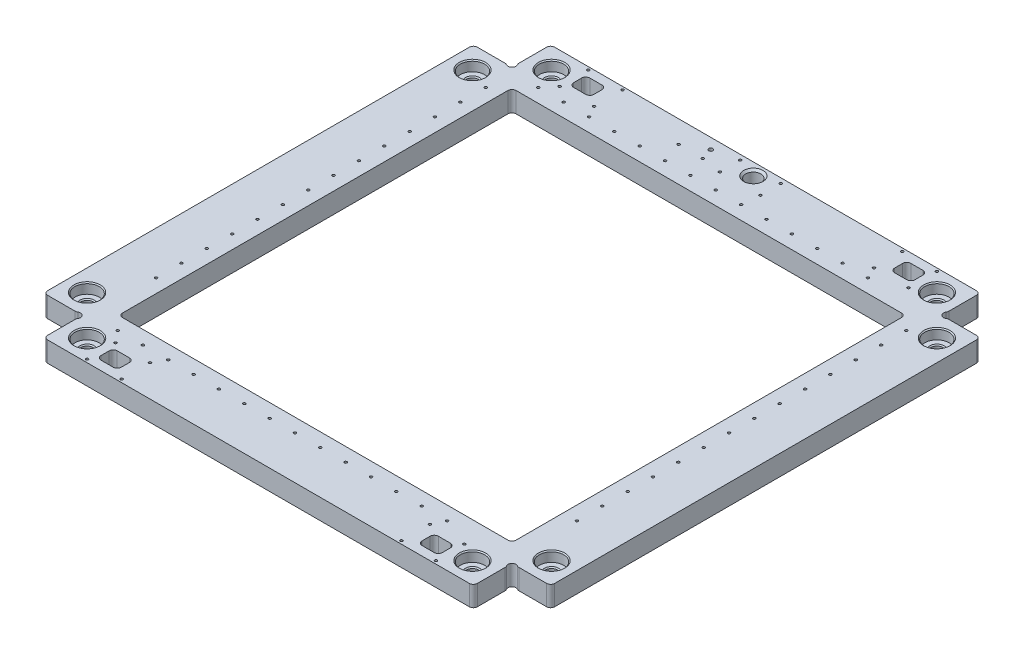
SolidWorks part; units mm, degrees
material "ASTM A36 Steel"
ref_plane "Front Plane" through (0, 0, 0) normal (0, 0, 1) x (1, 0, 0)
ref_plane "Top Plane" through (0, 0, 0) normal (0, 1, 0) x (1, 0, 0)
ref_plane "Right Plane" through (0, 0, 0) normal (1, 0, 0) x (0, 0, -1)
sketch "Sketch1" plane through (0, 0, 0) normal (0, 1, 0) x (1, 0, 0)
  line L1 (250, -250) -> (-250, -250)
  line L2 (250, -250) -> (250, 250)
  line L3 (250, 250) -> (-250, 250)
  line L4 (-250, -250) -> (-250, 250)
  line L5 (250, -250) -> (-250, 250) construction
  line L6 (250, 250) -> (-250, -250) construction
  point P0 (0, 0)
  dimension "D1" = 500
  dimension "D2" = 500
extrude "Boss-Extrude1" add sketch "Sketch1" along normal blind 20
sketch "Sketch2" plane through (0, 20, 0) normal (0, 1, 0) x (1, 0, 0)
  line L0 (250, 250) -> (-250, 250) construction
  line L10 (-250, 250) -> (-250, -250) construction
  line L15 (-250, 169) -> (-208, 169)
  line L16 (-250, 169) -> (-250, 211)
  line L17 (-174.5, 213.5) -> (-205.5, 213.5)
  line L27 (-250, 211) -> (-208, 211)
  line L33 (-208, 169) -> (-208, 211)
  line L35 (-250, 169) -> (-208, 211) construction
  line L36 (-250, 211) -> (-208, 169) construction
  line L37 (-169, 208) -> (-211, 208)
  line L38 (-169, 208) -> (-169, 250)
  line L39 (-169, 250) -> (-211, 250)
  line L40 (-211, 208) -> (-211, 250)
  line L41 (-169, 208) -> (-211, 250) construction
  line L42 (-169, 250) -> (-211, 208) construction
  line L43 (-208, 206) -> (-213, 211)
  line L44 (-174.5, 213.5) -> (-174.5, 244.5)
  line L45 (-174.5, 244.5) -> (-205.5, 244.5)
  line L46 (-205.5, 213.5) -> (-205.5, 244.5)
  line L47 (-174.5, 213.5) -> (-205.5, 244.5) construction
  line L48 (-174.5, 244.5) -> (-205.5, 213.5) construction
  line L49 (-213.5, 174.5) -> (-244.5, 174.5)
  line L50 (-213.5, 174.5) -> (-213.5, 205.5)
  line L51 (-213.5, 205.5) -> (-244.5, 205.5)
  line L52 (-244.5, 174.5) -> (-244.5, 205.5)
  line L53 (-213.5, 174.5) -> (-244.5, 205.5) construction
  line L54 (-213.5, 205.5) -> (-244.5, 174.5) construction
  line L55 (-206, 208) -> (-211, 213)
  line L56 (-213, 211) -> (-211, 213) construction
  point P1 (-229, 190)
  point P5 (-190, 229)
  point P23 (-229, 190)
  point P27 (-190, 229)
  dimension "D1" = 5
  dimension "D2" = 45
  dimension "D3" = 42
  dimension "D4" = 31
  dimension "D5" = 45
  dimension "D6" = 5
  dimension "D7" = 60
hole_wizard "Bearing Press Fit" positions "Sketch8" profile "Sketch9" hole size "Ø12.0" standard "ANSI Metric" end condition through all
sketch "Sketch8" plane through (0, 20, 0) normal (0, 1, 0) x (1, 0, 0)
  line L1 (-169, 250) -> (-211, 208) construction
  point P8 (-190, 229)
  point P12 (-229, 190)
sketch "Sketch9" plane through (-190, 20, -229) normal (1, 0, 0) x (0, 0, 1)
  line L0 (0, 0) -> (0, 20)
  line L1 (0, 20) -> (6, 20)
  line L2 (6, 20) -> (6, 0)
  line L5 (6, 0) -> (0, 0)
  line L11 (0, -6.35) -> (0, 107.95) construction
  dimension "Thru Hole Dia." = 12
  dimension "Thru Hole Depth" = 20
ref_axis "Axis1" through (0, 21, 0) along (0, -1, 0)
pattern_circular "CirPattern1" count 4 over 360 about axis through (0, 21, 0) along (0, -1, 0) of "Bearing Press Fit"
sketch "Sketch5" plane through (0, 20, 0) normal (0, 1, 0) x (1, 0, 0)
  line L1 (194, -194) -> (-194, -194)
  line L2 (194, -194) -> (194, 194)
  line L3 (194, 194) -> (-194, 194)
  line L4 (-194, -194) -> (-194, 194)
  line L5 (194, -194) -> (-194, 194) construction
  line L6 (194, 194) -> (-194, -194) construction
  point P0 (0, 0)
  dimension "D1" = 388
extrude "Cut-Extrude1" cut sketch "Sketch5" against normal up to surface (20 mm away) up to face at (-229, 0, 196)
sketch "Sketch10" plane through (0, 0, 0) normal (0, 1, 0) x (1, 0, 0)
  line L5 (194, 194) -> (-194, 194) construction
  line L6 (214, -214) -> (-214, -214)
  line L14 (214, -214) -> (214, 214)
  line L15 (214, 214) -> (-214, 214)
  line L16 (-214, -214) -> (-214, 214)
  line L17 (214, -214) -> (-214, 214) construction
  line L18 (214, 214) -> (-214, -214) construction
  line L19 (201.5, -201.5) -> (-201.5, -201.5)
  line L20 (201.5, -201.5) -> (201.5, 201.5)
  line L21 (201.5, 201.5) -> (-201.5, 201.5)
  line L22 (-201.5, -201.5) -> (-201.5, 201.5)
  line L23 (201.5, -201.5) -> (-201.5, 201.5) construction
  line L24 (201.5, 201.5) -> (-201.5, -201.5) construction
  point P0 (0, 0)
  point P6 (0, 0)
  dimension "D2" = 7.5
  dimension "D1" = 12.5
extrude "Linear Rail Slot" cut sketch "Sketch10" along normal blind 2.5
fillet "Fillet2" radius 4 4 edges at (-194, 10, 194) (194, 10, 194) (194, 10, -194) (-194, 10, -194)
sketch "Sketch11" plane through (0, 2.5, 0) normal (0, -1, 0) x (1, 0, 0)
  line L0 (-204, 207.5) -> (156, 207.5)
  line L1 (-201.5, 201.5) -> (201.5, 201.5) construction
  line L3 (-214, -214) -> (-214, 214) construction
  point P16 (143.5, 207.5)
  point P18 (118.5, 207.5)
  point P19 (93.5, 207.5)
  point P20 (68.5, 207.5)
  point P21 (43.5, 207.5)
  point P22 (18.5, 207.5)
  point P23 (-6.5, 207.5)
  point P24 (-31.5, 207.5)
  point P25 (-56.5, 207.5)
  point P26 (-81.5, 207.5)
  point P28 (-106.5, 207.5)
  point P29 (-131.5, 207.5)
  point P30 (-156.5, 207.5)
  point P31 (-181.5, 207.5)
  dimension "D1" = 360
  dimension "D2" = 6
  dimension "D4" = 14
  dimension "D5" = 25
  dimension "D6" = 10
  dimension "D3" = 12.5
hole_wizard "Tap Drill for M3x0.5 Tap1" positions "Sketch12" profile "Sketch13" hole size "M3x0.5" standard "ANSI Metric" end condition through all
sketch "Sketch12" plane through (0, 2.5, 0) normal (0, -1, 0) x (-1, 0, 0)
  line L0 (204, -207.5) -> (-156, -207.5) construction
  point P28 (-143.5, -207.5)
  point P31 (-118.5, -207.5)
  point P34 (-93.5, -207.5)
  point P37 (-68.5, -207.5)
  point P40 (-43.5, -207.5)
  point P43 (-18.5, -207.5)
  point P46 (6.5, -207.5)
  point P49 (31.5, -207.5)
  point P51 (56.5, -207.5)
  point P54 (81.5, -207.5)
  point P57 (106.5, -207.5)
  point P61 (131.5, -207.5)
  point P64 (156.5, -207.5)
  point P67 (181.5, -207.5)
sketch "Sketch13" plane through (143.5, 2.5, 207.5) normal (1, 0, 0) x (0, 0, -1)
  line L0 (0, 0) -> (0, 17.5)
  line L1 (0, 17.5) -> (1.25, 17.5)
  line L2 (1.25, 17.5) -> (1.25, 0)
  line L5 (1.25, 0) -> (0, 0)
  line L11 (0, -6.35) -> (0, 107.95) construction
  dimension "Thru Hole Dia." = 2.5
  dimension "Thru Hole Depth" = 17.5
sketch "Sketch14" plane through (0, 0, 0) normal (0, -1, 0) x (1, 0, 0)
  line L1 (-156.5, 213.5) -> (-181.5, 213.5)
  line L2 (-152.5, 217.5) -> (-152.5, 219.5)
  line L3 (-156.5, 223.5) -> (-181.5, 223.5)
  line L4 (-185.5, 217.5) -> (-185.5, 219.5)
  line L5 (-152.5, 213.5) -> (-185.5, 223.5) construction
  line L6 (-152.5, 223.5) -> (-185.5, 213.5) construction
  line L7 (-201.5, 201.5) -> (201.5, 201.5) construction
  line L8 (-181.5, 207.5) -> (-156.5, 207.5) construction
  line L19 (-6.5, 213.5) -> (-31.5, 213.5)
  line L25 (-2.5, 217.5) -> (-2.5, 219.5)
  line L26 (-6.5, 223.5) -> (-31.5, 223.5)
  line L31 (-35.5, 217.5) -> (-35.5, 219.5)
  line L32 (-2.5, 213.5) -> (-35.5, 223.5) construction
  line L33 (-2.5, 223.5) -> (-35.5, 213.5) construction
  line L34 (-31.5, 207.5) -> (-6.5, 207.5) construction
  line L35 (143.5, 213.5) -> (118.5, 213.5)
  line L36 (147.5, 217.5) -> (147.5, 219.5)
  line L37 (143.5, 223.5) -> (118.5, 223.5)
  line L38 (114.5, 217.5) -> (114.5, 219.5)
  line L39 (147.5, 213.5) -> (114.5, 223.5) construction
  line L40 (147.5, 223.5) -> (114.5, 213.5) construction
  line L41 (118.5, 207.5) -> (143.5, 207.5) construction
  arc A3 (-152.5, 219.5) -> (-156.5, 223.5) centre (-156.5, 219.5) ccw
  arc A4 (-156.5, 213.5) -> (-152.5, 217.5) centre (-156.5, 217.5) ccw
  arc A5 (-181.5, 213.5) -> (-185.5, 217.5) centre (-181.5, 217.5) cw
  arc A6 (-181.5, 223.5) -> (-185.5, 219.5) centre (-181.5, 219.5) ccw
  arc A7 (-2.5, 219.5) -> (-6.5, 223.5) centre (-6.5, 219.5) ccw
  arc A8 (-6.5, 213.5) -> (-2.5, 217.5) centre (-6.5, 217.5) ccw
  arc A9 (-31.5, 213.5) -> (-35.5, 217.5) centre (-31.5, 217.5) cw
  arc A10 (-31.5, 223.5) -> (-35.5, 219.5) centre (-31.5, 219.5) ccw
  arc A11 (147.5, 219.5) -> (143.5, 223.5) centre (143.5, 219.5) ccw
  arc A12 (143.5, 213.5) -> (147.5, 217.5) centre (143.5, 217.5) ccw
  arc A13 (118.5, 213.5) -> (114.5, 217.5) centre (118.5, 217.5) cw
  arc A14 (118.5, 223.5) -> (114.5, 219.5) centre (118.5, 219.5) ccw
  point P0 (-169, 218.5)
  point P12 (-169, 207.5)
  point P26 (-19, 218.5)
  point P45 (131, 218.5)
  dimension "D5" = 3
  dimension "D4" = 4
  dimension "D1" = 33
  dimension "D2" = 12
  dimension "D3" = 10
  dimension "D7" = 25
  dimension "D6" = 150
mirror "Mirror5" about plane through (0, 0, 0) normal (0, 0, 1) of "Tap Drill for M3x0.5 Tap1"
ref_plane "Plane1" through (0, 0, 0) normal (-0.7071, 0, 0.7071) x (0.7071, 0, 0.7071)
mirror "Mirror6" about plane through (0, 0, 0) normal (-0.7071, 0, 0.7071) of "Mirror5"
sketch "Sketch19" plane through (0, 2.5, 0) normal (0, -1, 0) x (1, 0, 0)
  line L0 (-198.5, 201.5) -> (-198.5, 214)
  line L1 (-201.5, 201.5) -> (201.5, 201.5) construction
  line L2 (-214, 214) -> (214, 214) construction
  line L3 (-198.5, 214) -> (-214, 214)
  line L4 (-214, 214) -> (-214, 198.5)
  line L5 (-214, -214) -> (-214, 214) construction
  line L6 (-214, 198.5) -> (-201.5, 198.5)
  line L7 (-201.5, -201.5) -> (-201.5, 201.5) construction
  line L8 (-201.5, 198.5) -> (-201.5, 201.5)
  line L9 (-201.5, 201.5) -> (-198.5, 201.5)
  dimension "D1" = 3
extrude "Boss-Extrude2" add sketch "Sketch19" along normal up to surface (2.5 mm away) up to face at (-229, 0, 196)
pattern_circular "CirPattern4" count 4 over 360 about axis through (0, 21, 0) along (0, -1, 0) of "Boss-Extrude2"
sketch "Sketch20" plane through (0, 20, 0) normal (0, 1, 0) x (1, 0, 0)
  line L5 (-250, -250) -> (250, -250) construction
  line L20 (148.3, -225) -> (168.3, -241) construction
  line L23 (168.3, -225) -> (148.3, -241) construction
  line L28 (122, -247) -> (172, -219) construction
  line L29 (172, -247) -> (122, -219) construction
  line L30 (172, -219) -> (122, -219) construction
  line L31 (122, -247) -> (122, -219) construction
  line L32 (172, -247) -> (122, -247) construction
  line L33 (172, -247) -> (172, -219) construction
  line L34 (164.3, -241) -> (152.3, -241)
  line L35 (148.3, -229) -> (148.3, -237)
  line L36 (164.3, -225) -> (152.3, -225)
  line L37 (168.3, -229) -> (168.3, -237)
  arc A12 (152.3, -225) -> (148.3, -229) centre (152.3, -229) ccw
  arc A13 (148.3, -237) -> (152.3, -241) centre (152.3, -237) ccw
  arc A14 (168.3, -237) -> (164.3, -241) centre (164.3, -237) cw
  arc A15 (168.3, -229) -> (164.3, -225) centre (164.3, -229) ccw
  circle A16 centre (190, -229) radius 6 construction
  point P65 (158.3, -233)
  point P66 (147, -233)
  point P67 (158.3, -233)
  dimension "D7" = 31.7
  dimension "D8" = 11.3
  dimension "D6" = 4
  dimension "D1" = 28
  dimension "D2" = 50
  dimension "D3" = 17
  dimension "D4" = 20
  dimension "D5" = 16
extrude "Cut-Extrude3" cut sketch "Sketch20" against normal through all
hole_wizard "Tap Drill for M3x0.5 Tap6" positions "Sketch39" profile "Sketch40" hole size "M3x0.5" standard "ANSI Metric"
sketch "Sketch39" plane through (0, 20, 0) normal (0, 1, 0) x (1, 0, 0)
  line L1 (172, -247) -> (138, -247)
  line L2 (172, -247) -> (172, -219)
  line L3 (172, -219) -> (138, -219)
  line L4 (138, -247) -> (138, -219)
  line L5 (-250, -250) -> (250, -250) construction
  circle A0 centre (190, -229) radius 6 construction
  point P1 (172, -247)
  point P2 (138, -219)
  point P99 (172, -219)
  point P100 (138, -247)
  dimension "D1" = 34
  dimension "D2" = 28
  dimension "D3" = 3
  dimension "D4" = 18
sketch "Sketch40" plane through (172, 20, 247) normal (1, 0, 0) x (0, 0, 1)
  line L0 (0, 0) -> (0, 20)
  line L1 (0, 20) -> (1.25, 20)
  line L2 (1.25, 20) -> (1.25, 0)
  line L5 (1.25, 0) -> (0, 0)
  line L10 (0, 20) -> (-1.25, 20) construction
  line L11 (0, -6.35) -> (0, 107.95) construction
  dimension "Hole Dia." = 2.5
  dimension "Hole Depth" = 20
  dimension "Drill Angle" = 180
mirror "Mirror8" about plane through (0, 0, 0) normal (1, 0, 0) of "Tap Drill for M3x0.5 Tap6", "Cut-Extrude3"
mirror "Mirror9" about plane through (0, 0, 0) normal (0, 0, 1) of "Mirror8"
sketch "Sketch27" plane through (0, 20, 0) normal (0, 1, 0) x (1, 0, 0)
  line L1 (250, -250) -> (211.9, -250)
  line L2 (250, -250) -> (250, -211.9)
  line L3 (250, -211.9) -> (211.9, -211.9)
  line L4 (211.9, -250) -> (211.9, -211.9)
  dimension "D1" = 38.1
extrude "Cut-Extrude4" cut sketch "Sketch27" against normal up to surface (20 mm away) up to face at (172, 0, -245.75)
sketch "Sketch47" plane through (0, 0, 0) normal (0, -1, 0) x (1, 0, 0)
  line L0 (211.9, 211.9) -> (214.7284, 214.7284) construction
  line L1 (211.9, 211.9) -> (250, 211.9) construction
  circle A0 centre (214.7284, 214.7284) radius 4
  dimension "D1" = 8
  dimension "D2" = 45
extrude "Cut-Extrude5" cut sketch "Sketch47" against normal up to surface (20 mm away) up to face at (70.6333, 20, 70.6333)
pattern_circular "CirPattern3" count 4 over 360 about axis through (0, 21, 0) along (0, -1, 0) of "Cut-Extrude4", "Cut-Extrude5"
fillet "Fillet5" radius 4 16 edges at (198.5, 1.25, 214) (198.5, 1.25, 201.5) (201.5, 1.25, 198.5) (214, 1.25, 198.5) (-214, 1.25, 198.5) (-198.5, 1.25, 214) (-201.5, 1.25, 198.5) (-198.5, 1.25, 201.5) (-214, 1.25, -198.5) (-198.5, 1.25, -214) (-198.5, 1.25, -201.5) (-201.5, 1.25, -198.5) (198.5, 1.25, -201.5) (198.5, 1.25, -214) (201.5, 1.25, -198.5) (214, 1.25, -198.5)
hole_wizard "Tap Drill for M3x0.5 Tap4" positions "Sketch35" profile "Sketch36" hole size "M3x0.5" standard "ANSI Metric" end condition up to next
sketch "Sketch35" plane through (0, 20, 0) normal (0, 1, 0) x (1, 0, 0)
  line L1 (20, 225) -> (-20, 225)
  line L2 (20, 225) -> (20, 245)
  line L3 (20, 245) -> (-20, 245)
  line L4 (-20, 225) -> (-20, 245)
  line L5 (20, 225) -> (-20, 245) construction
  line L6 (20, 245) -> (-20, 225) construction
  line L7 (211.9, 250) -> (-211.9, 250) construction
  point P2 (-20, 245)
  point P53 (20, 225)
  point P54 (20, 245)
  point P55 (-20, 225)
  point P69 (0, 235)
  dimension "D1" = 20
  dimension "D2" = 40
  dimension "D3" = 15
sketch "Sketch36" plane through (-20, 20, -245) normal (1, 0, 0) x (0, 0, 1)
  line L0 (0, 0) -> (0, 20)
  line L1 (0, 20) -> (1.25, 20)
  line L2 (1.25, 20) -> (1.25, 0)
  line L5 (1.25, 0) -> (0, 0)
  line L11 (0, -6.35) -> (0, 107.95) construction
  dimension "Thru Hole Dia." = 2.5
  dimension "Thru Hole Depth" = 20
hole_wizard "Ø15.0 (15) Diameter Hole2" positions "Sketch37" profile "Sketch38" hole size "Ø15.0" standard "ANSI Metric" end condition up to next
sketch "Sketch37" plane through (0, 20, 0) normal (0, 1, 0) x (1, 0, 0)
  circle A0 centre (0, 235) radius 1.25 construction
  point P0 (0, 238)
  dimension "D1" = 3
sketch "Sketch38" plane through (0, 20, -238) normal (1, 0, 0) x (0, 0, 1)
  line L0 (0, 0) -> (0, 20)
  line L1 (0, 20) -> (7.5, 20)
  line L2 (7.5, 20) -> (7.5, 0)
  line L5 (7.5, 0) -> (0, 0)
  line L11 (0, -6.35) -> (0, 107.95) construction
  dimension "Thru Hole Dia." = 15
  dimension "Thru Hole Depth" = 20
chamfer "Chamfer1" distance 2 angle 45 2 edges at (0, 0, -230.5) (0, 20, -230.5)
hole_wizard "Ø24.0 (24) Diameter Hole1" positions "Sketch41" profile "Sketch42" hole size "Ø24.0" standard "ANSI Metric"
sketch "Sketch41" plane through (0, 20, 0) normal (0, 1, 0) x (1, 0, 0)
  point P0 (-229, -190)
  point P3 (-190, -229)
  point P6 (190, -229)
  point P9 (229, -190)
  point P12 (229, 190)
  point P15 (190, 229)
  point P18 (-190, 229)
  point P21 (-229, 190)
sketch "Sketch42" plane through (-229, 20, 190) normal (1, 0, 0) x (0, 0, 1)
  line L0 (0, 0) -> (0, 10)
  line L1 (0, 10) -> (12, 10)
  line L2 (12, 10) -> (12, 0)
  line L5 (12, 0) -> (0, 0)
  line L10 (0, 10) -> (-12, 10) construction
  line L11 (0, -6.35) -> (0, 107.95) construction
  dimension "Hole Dia." = 24
  dimension "Hole Depth" = 10
  dimension "Drill Angle" = 180
chamfer "Chamfer2" distance 1 angle 45 24 edges at (-229, 0, -184) (-229, 10, -196) (-190, 0, -223) (-190, 10, -235) (229, 0, -184) (229, 10, -196) (190, 0, -223) (190, 10, -235) (229, 0, 196) (229, 10, 184) (190, 0, 235) (190, 10, 223) (-190, 0, 235) (-190, 10, 223) (-229, 0, 196) (-229, 10, 184) (-229, 20, -178) (-190, 20, -217) (229, 20, -178) (190, 20, -217) (229, 20, 202) (190, 20, 241) (-190, 20, 241) (-229, 20, 202)
fillet "Fillet6" radius 4 16 edges at (250, 10, -211.9) (211.9, 10, -250) (-211.9, 10, -250) (-250, 10, -211.9) (211.9, 10, 250) (250, 10, 211.9) (-211.9, 10, 250) (-250, 10, 211.9) (-217.5569, 10, 211.9) (-217.5569, 10, -211.9) (-211.9, 10, -217.5569) (211.9, 10, -217.5569) (217.5569, 10, -211.9) (211.9, 10, 217.5569) (-211.9, 10, 217.5569) (217.5569, 10, 211.9)
hole_wizard "Tap Drill for M3x0.5 Tap7" positions "Sketch43" profile "Sketch44" hole size "M3x0.5" standard "ANSI Metric" end condition up to next
sketch "Sketch43" plane through (0, 20, 0) normal (0, 1, 0) x (1, 0, 0)
  line L0 (-63.7737, 228) -> (-39.7737, 228) construction
  line L2 (207.9, 250) -> (-207.9, 250) construction
  circle A0 centre (-20, 225) radius 1.25 construction
  point P1 (-63.7737, 228)
  point P2 (-39.7737, 228)
  dimension "D3" = 20
  dimension "D1" = 22
  dimension "D2" = 24
sketch "Sketch44" plane through (-63.7737, 20, -228) normal (1, 0, 0) x (0, 0, 1)
  line L0 (0, 0) -> (0, 20)
  line L1 (0, 20) -> (1.25, 20)
  line L2 (1.25, 20) -> (1.25, 0)
  line L5 (1.25, 0) -> (0, 0)
  line L11 (0, -6.35) -> (0, 107.95) construction
  dimension "Thru Hole Dia." = 2.5
  dimension "Thru Hole Depth" = 20
hole_wizard "Ø4.0 (4) Diameter Hole1" positions "Sketch45" profile "Sketch46" hole size "Ø4.0" standard "ANSI Metric" end condition up to next
sketch "Sketch45" plane through (0, 20, 0) normal (0, 1, 0) x (1, 0, 0)
  circle A0 centre (-63.7737, 228) radius 1.25 construction
  point P0 (-43.4737, 239.5)
  dimension "D1" = 20.3
  dimension "D2" = 11.5
sketch "Sketch46" plane through (-43.4737, 20, -239.5) normal (1, 0, 0) x (0, 0, 1)
  line L0 (0, 0) -> (0, 20)
  line L1 (0, 20) -> (2, 20)
  line L2 (2, 20) -> (2, 0)
  line L5 (2, 0) -> (0, 0)
  line L11 (0, -6.35) -> (0, 107.95) construction
  dimension "Thru Hole Dia." = 4
  dimension "Thru Hole Depth" = 20
